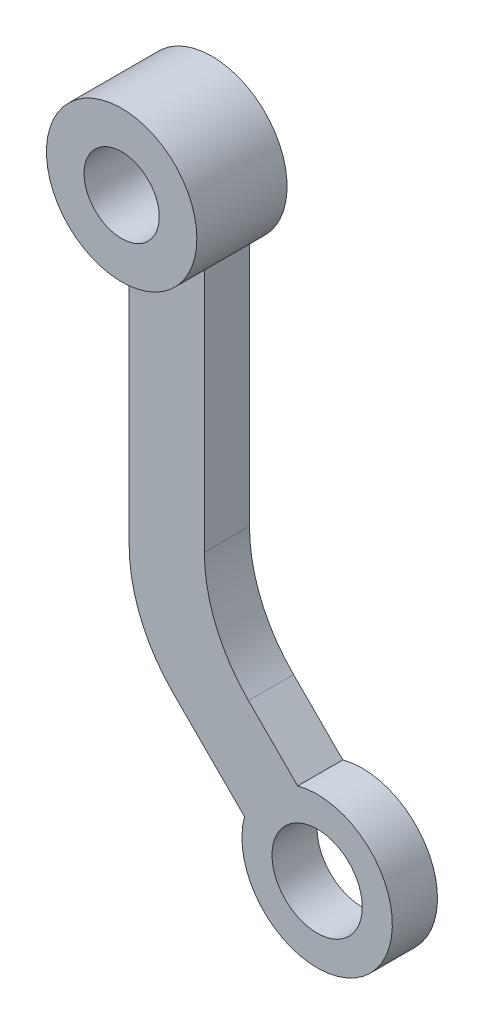
SolidWorks part; units mm, degrees
ref_plane "Front Plane" through (0, 0, 0) normal (0, 0, 1) x (1, 0, 0)
ref_plane "Top Plane" through (0, 0, 0) normal (0, 1, 0) x (1, 0, 0)
ref_plane "Right Plane" through (0, 0, 0) normal (1, 0, 0) x (0, 0, -1)
sketch "Sketch1" plane through (0, 0, 0) normal (0, 0, 1) x (1, 0, 0)
  line L2 (-3.75, 15.8349) -> (-3.75, 7.5888)
  line L3 (-6.25, 15.8349) -> (-6.25, 6.5533)
  line L4 (-5, 15.5) -> (-5, 3.2322) construction
  line L5 (0, 0) -> (0, 2.5) construction
  line L6 (0, 0) -> (-8.593, 8.593) construction
  line L7 (-2.4148, 0.647) -> (-4.7855, 3.0178)
  line L8 (-0.647, 2.4148) -> (-2.2855, 4.0533)
  arc A4 (-2.4148, 0.647) -> (-0.647, 2.4148) centre (0, 0) ccw
  circle A5 centre (-5, 18) radius 2.5
  circle A6 centre (-5, 18) radius 1.25
  circle A7 centre (0, 0) radius 1.5
  arc A8 (-2.2855, 4.0533) -> (-3.75, 7.5888) centre (1.25, 7.5888) cw
  arc A9 (-6.25, 6.5533) -> (-4.7855, 3.0178) centre (-1.25, 6.5533) ccw
  point P0 (0, 0)
  point P11 (0, 0)
  dimension "D2" = 2.5
  dimension "D3" = 3
  dimension "D7" = 5
  dimension "D8" = 5
  dimension "D14" = 5
  dimension "D4" = 18
  dimension "D5" = 1.25
  dimension "D9" = 5
  dimension "D10" = 1.25
  dimension "D11" = 2.5
  dimension "D12" = 45
  dimension "D13" = 1.25
extrude "Boss-Extrude1" add sketch "Sketch1" along normal blind 1.5 contours L3 A9 L7 A4 L8 A8 L2 A5 A7 region at (-3.9532, 11.7119, 0)
extrude "Boss-Extrude2" add sketch "Sketch1<3>" along normal blind 3 contours A5 A6 region at (-5, 15.5707, 0)
sketch "Sketch1<3>" plane through (0, 0, 0) normal (0, 0, 1) x (1, 0, 0) same geometry as "Sketch1"
